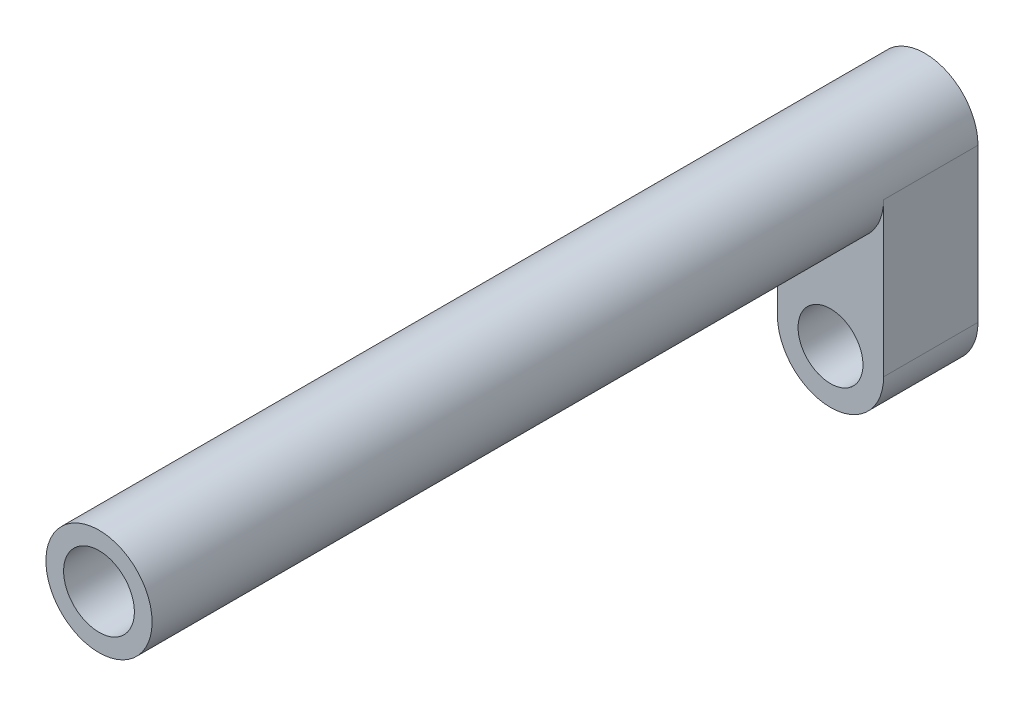
SolidWorks part; units mm, degrees
ref_plane "Front Plane" through (0, 0, 0) normal (0, 0, 1) x (1, 0, 0)
ref_plane "Top Plane" through (0, 0, 0) normal (0, 1, 0) x (1, 0, 0)
ref_plane "Right Plane" through (0, 0, 0) normal (1, 0, 0) x (0, 0, -1)
sketch "Sketch1" plane through (0, 0, 0) normal (0, 0, 1) x (1, 0, 0)
  line L0 (0, -2.6513) -> (0, 3.8487) construction
  line L1 (-2.25, -2.6513) -> (-2.25, 3.8487)
  line L2 (2.25, -2.6513) -> (2.25, 3.8487)
  arc A0 (-2.25, -2.6513) -> (2.25, -2.6513) centre (0, -2.6513) ccw
  arc A1 (2.25, 3.8487) -> (-2.25, 3.8487) centre (0, 3.8487) ccw
  circle A2 centre (0, 3.8487) radius 1.5
  circle A3 centre (0, -2.6513) radius 1.375
  arc A4 (-2.25, 3.8487) -> (2.25, 3.8487) centre (0, 3.8487) ccw
  point P3 (0, 0.5987)
  dimension "D1" = 6.5
  dimension "D2" = 3
  dimension "D3" = 2.75
  dimension "D4" = 4.5
extrude "Boss-Extrude1" add sketch "Sketch1" along normal blind 4 contours A3 A4 L1 A0 L2 region at (0, -0.7906, 0)
extrude "Boss-Extrude3" add sketch "Sketch1<4>" along normal blind 35 contours A1 A4 A2 region at (0, 6.0351, 0)
sketch "Sketch1<4>" plane through (0, 0, 0) normal (0, 0, 1) x (1, 0, 0) same geometry as "Sketch1"
